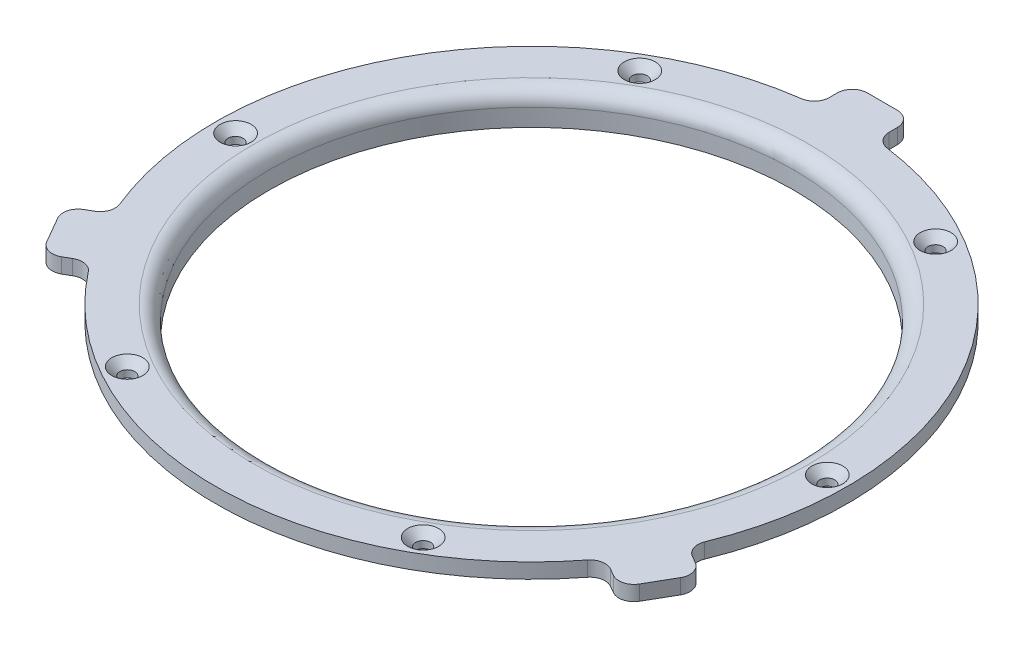
SolidWorks part; units mm, degrees
material "PET"
ref_plane "Front Plane" through (0, 0, 0) normal (0, 0, 1) x (1, 0, 0)
ref_plane "Top Plane" through (0, 0, 0) normal (0, 1, 0) x (1, 0, 0)
ref_plane "Right Plane" through (0, 0, 0) normal (1, 0, 0) x (0, 0, -1)
sketch "Sketch2" plane through (0, 0, 0) normal (0, 0, 1) x (1, 0, 0)
  line L0 (-55, 8.3) -> (-52.5, 8.3)
  line L1 (-52.5, 8.3) -> (-52.5, 14.8)
  line L2 (-52.5, 14.8) -> (-63.2, 14.8)
  line L3 (-63.2, 14.8) -> (-63.2, 11.8)
  line L4 (-63.2, 11.8) -> (-55, 11.8)
  line L5 (-55, 11.8) -> (-55, 8.3)
  line L11 (0, 0) -> (0, 30.013) construction
sketch "Sketch3" plane through (0, 0, 0) normal (0, 0, 1) x (1, 0, 0)
  line L6 (-55, 8.3) -> (-52.5, 8.3)
  line L7 (-52.5, 8.3) -> (-52.5, 14.8)
  line L8 (-52.5, 14.8) -> (-63.2, 14.8)
  line L9 (-63.2, 14.8) -> (-63.2, 11.8)
  line L10 (-63.2, 11.8) -> (-55, 11.8)
  line L11 (-55, 11.8) -> (-55, 8.3)
  line L12 (-55, 8.3) -> (-52.5, 8.3)
  line L13 (-52.5, 8.3) -> (-52.5, 14.8)
  line L14 (-52.5, 14.8) -> (-63.2, 14.8)
  line L15 (-63.2, 14.8) -> (-63.2, 11.8)
  line L16 (-63.2, 11.8) -> (-55, 11.8)
  line L17 (-55, 11.8) -> (-55, 8.3)
  dimension "D1" = 0
revolve "Cap" add sketch "Sketch3" angle 360 about L11
sketch "Sketch9" plane through (0, 0, 0) normal (0, 0, 1) x (1, 0, 0)
  line L0 (-63.2, 11.8) -> (-55.2, 11.8) construction
  line L4 (-59.2, 11.8) -> (-59.2, 0.8)
  line L5 (-59.2, 11.8) -> (-58, 11.8)
  line L6 (-59.2, 11.8) -> (-57.1, 11.8)
  point P3 (-59.2, 11.8)
sketch "Sketch10" plane through (0, 0, 0) normal (0, 1, 0) x (1, 0, 0)
  circle A0 centre (-59.2, 0) radius 2.1
  point P0 (-59.2, 0)
  point P1 (-57.1, 0)
hole_wizard "CSK for M3 Flat Head Machine Screw1" positions "Sketch11" profile "Sketch12" countersink size "M3" standard "ANSI Metric"
sketch "Sketch11" plane through (0, 14.8, 0) normal (0, 1, 0) x (1, 0, 0)
  point P0 (-59.2, 0)
sketch "Sketch12" plane through (-59.2, 14.8, 0) normal (1, 0, 0) x (0, 0, 1)
  line L0 (0, 0) -> (0, 9.7913)
  line L1 (0, 9.7913) -> (1.5, 8.89)
  line L2 (1.5, 8.89) -> (1.5, 1.6)
  line L3 (1.5, 1.6) -> (3.1, 0)
  line L5 (3.1, 0) -> (0, 0)
  line L6 (-1.5, 1.6) -> (-3.1, 0) construction
  line L10 (0, 9.7913) -> (-1.5, 8.89) construction
  line L11 (0, -6.35) -> (0, 107.95) construction
  dimension "Hole Dia." = 3
  dimension "Hole Depth" = 8.89
  dimension "Near C'Sink Dia." = 6.2
  dimension "Near C'Sink Angle" = 90
  dimension "Drill Angle" = 118
pattern_circular "CirPattern1" count 6 over 360 about axis through (0, 0, 0) along (0, 1, 0) of "CSK for M3 Flat Head Machine Screw1" reverse direction yes
fillet "Fillet1" radius 3 1 edges at (52.5, 14.8, 0)
sketch "Sketch13" plane through (0, 0, 0) normal (0, 0, 1) x (1, 0, 0)
  line L0 (-63.2, 9.8) -> (-70.2, 9.8)
  line L2 (-70.2, 9.8) -> (-70.2, -3.2)
  line L3 (-70.2, -3.2) -> (-63.2, -3.2)
  line L4 (-63.2, -3.2) -> (-63.2, 9.8)
  line L6 (0, 0) -> (0, 30.013) construction
sketch "Sketch14" plane through (0, 0, 0) normal (0, 1, 0) x (1, 0, 0)
  line L0 (-70.2, 0) -> (-63.2, 0) construction
  line L1 (-70.2, 0) -> (-63.2, 0) construction
  line L2 (-63.2, 0) -> (-70.2, 0) construction
  line L3 (-63.795, -29.9038) -> (-57.795, -40.2962)
  line L4 (-63.795, -29.9038) -> (-57.4856, -26.2611)
  line L5 (-57.795, -40.2962) -> (-51.4856, -36.6534)
  line L6 (-57.4856, -26.2611) -> (-51.4856, -36.6534)
  point P5 (-60.795, -35.1)
  dimension "D1" = 12
extrude "Boss-Extrude1" add sketch "Sketch14" against normal up to surface (-11.8 mm away) from surface up to face at (-31.1, 11.8, 51.2687) starting at face at (55.5, 14.8, 0)
fillet "Fillet2" radius 3 4 edges at (-57.4856, 13.3, 26.2611) (-63.795, 13.3, 29.9038) (-57.795, 13.3, 40.2962) (-51.4856, 13.3, 36.6534)
pattern_circular "CirPattern2" count 3 over 360 about axis through (0, 0, 0) along (0, 1, 0) of "Boss-Extrude1", "Fillet2" reverse direction yes
equation "\"TopHoles\"= 6"
equation "\"D1@CirPattern1\"=\"TopHoles\""
